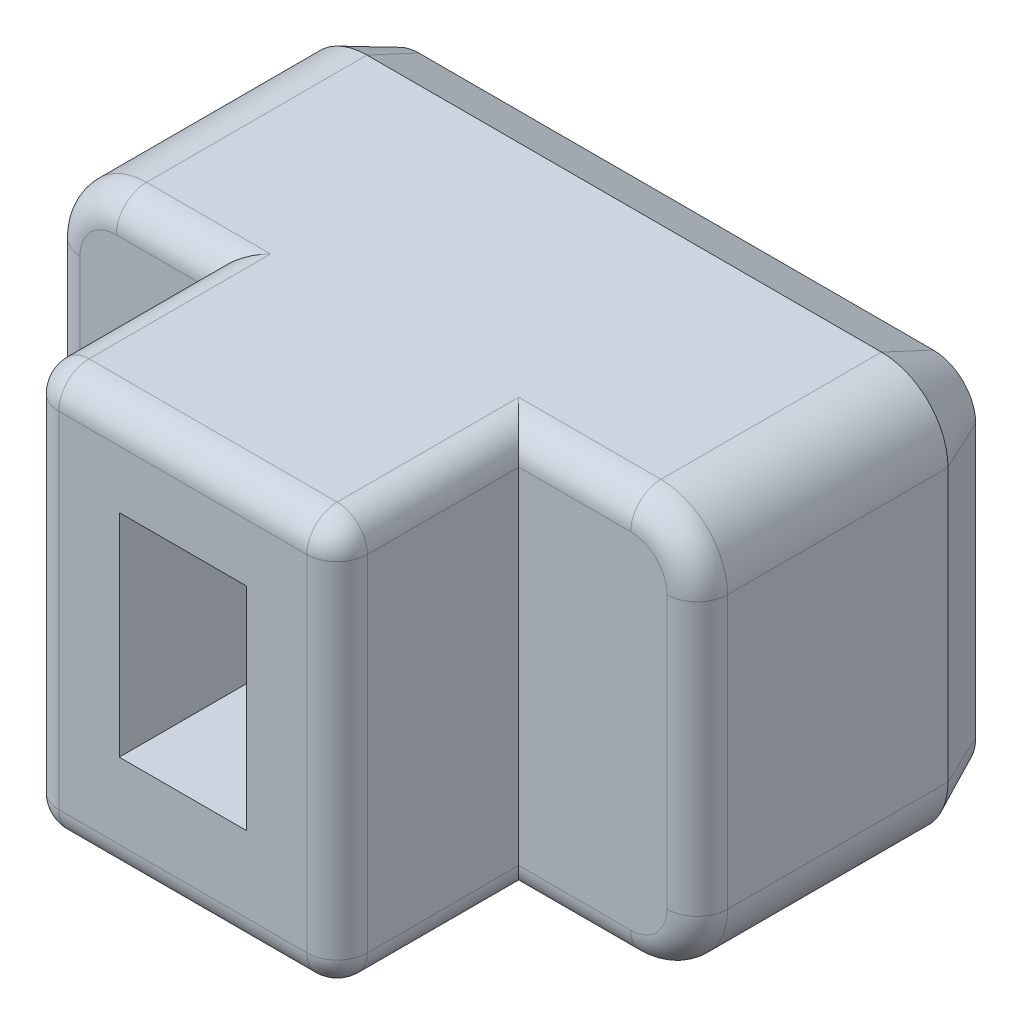
SolidWorks part; units mm, degrees
ref_plane "Plan de face" through (0, 0, 0) normal (0, 0, 1) x (1, 0, 0)
ref_plane "Plan de dessus" through (0, 0, 0) normal (0, 1, 0) x (1, 0, 0)
ref_plane "Plan de droite" through (0, 0, 0) normal (1, 0, 0) x (0, 0, -1)
sketch "Esquisse2" plane through (0, 0, 0) normal (0, 0, 1) x (1, 0, 0)
  line L1 (1.1, 0) -> (9.6, 0)
  line L2 (0, 1.1) -> (0, 5.6)
  line L3 (1.1, 6.7) -> (9.6, 6.7)
  line L4 (10.7, 1.1) -> (10.7, 5.6)
  arc A0 (9.6, 6.7) -> (10.7, 5.6) centre (9.6, 5.6) cw
  arc A1 (9.6, 0) -> (10.7, 1.1) centre (9.6, 1.1) ccw
  arc A2 (1.1, 0) -> (0, 1.1) centre (1.1, 1.1) cw
  arc A3 (0, 5.6) -> (1.1, 6.7) centre (1.1, 5.6) cw
  point P7 (10.7, 6.7)
  point P12 (0, 0)
  point P15 (0, 6.7)
  dimension "D3" = 1.1
  dimension "D1" = 10.7
  dimension "D2" = 6.7
extrude "Boss.-Extru.1" add sketch "Esquisse2" along normal blind 8
sketch "Esquisse3" plane through (0, 0, 8) normal (0, 0, 1) x (1, 0, 0)
  line L0 (0, 5.6) -> (0, 1.1) construction
  line L1 (4.15, 5.25) -> (6.25, 5.25)
  line L2 (4.15, 5.25) -> (4.15, 1.75)
  line L3 (4.15, 1.75) -> (6.25, 1.75)
  line L4 (6.25, 5.25) -> (6.25, 1.75)
  line L5 (10.7, 1.1) -> (10.7, 5.6) construction
  line L6 (9.6, 6.7) -> (1.1, 6.7) construction
  line L7 (1.1, 0) -> (9.6, 0) construction
  dimension "D1" = 2.1
  dimension "D2" = 3.5
  dimension "D3" = 4.15
  dimension "D4" = 4.45
  dimension "D5" = 1.45
  dimension "D6" = 1.75
extrude "Enlèv. mat.-Extru.1" cut sketch "Esquisse3" against normal blind 3
sketch "Esquisse4" plane through (0, 0, 8) normal (0, 0, 1) x (1, 0, 0)
  line L0 (2.65, 6.7) -> (2.65, 0)
  line L1 (9.6, 6.7) -> (1.1, 6.7) construction
  line L2 (1.1, 0) -> (9.6, 0) construction
  line L3 (2.65, 0) -> (7.75, 0)
  line L4 (7.75, 0) -> (7.75, 6.7)
  line L5 (7.75, 6.7) -> (2.65, 6.7)
  line L6 (4.15, 5.25) -> (4.15, 1.75) construction
  line L7 (6.25, 1.75) -> (6.25, 5.25) construction
  dimension "D1" = 1.5
  dimension "D2" = 1.5
extrude "Enlèv. mat.-Extru.2" cut sketch "Esquisse4" against normal blind 3 flip side to cut
fillet "Congé1" radius 0.5 18 edges at (8.675, 0, 5) (10.3778, 0.3222, 5) (10.7, 3.35, 5) (10.3778, 6.3778, 5) (1.875, 6.7, 5) (0.3222, 6.3778, 5) (1.875, 0, 5) (0.3222, 0.3222, 5) (7.75, 6.7, 6.5) (2.65, 6.7, 6.5) (7.75, 0, 6.5) (2.65, 0, 6.5) (2.65, 3.35, 8) (5.2, 6.7, 8) (7.75, 3.35, 8) (5.2, 0, 8) (8.675, 6.7, 5) (0, 3.35, 5)
chamfer "Chanfrein1" distance 0.4 angle 65 8 edges at (5.35, 0, 0) (10.3778, 0.3222, 0) (0.3222, 0.3222, 0) (10.7, 3.35, 0) (0, 3.35, 0) (10.3778, 6.3778, 0) (0.3222, 6.3778, 0) (5.35, 6.7, 0) first distance on face at (5.35, 3.35, 0)
sketch "Esquisse5" plane through (0, 0, 0) normal (0, 0, 1) x (1, 0, 0)
  line L0 (-0.9378, 5.3566) -> (11.6517, 5.3566) construction
  text T0 "ALT" font "Century Gothic" height 4
extrude "Enlèv. mat.-Extru.3" cut sketch "Esquisse5" along normal blind 0.2
extrude "Boss.-Extru.2" add sketch "Esquisse5<4>" against normal blind 0.2
sketch "Esquisse5<4>" plane through (0, 0, 0) normal (0, 0, 1) x (1, 0, 0) same geometry as "Esquisse5"
